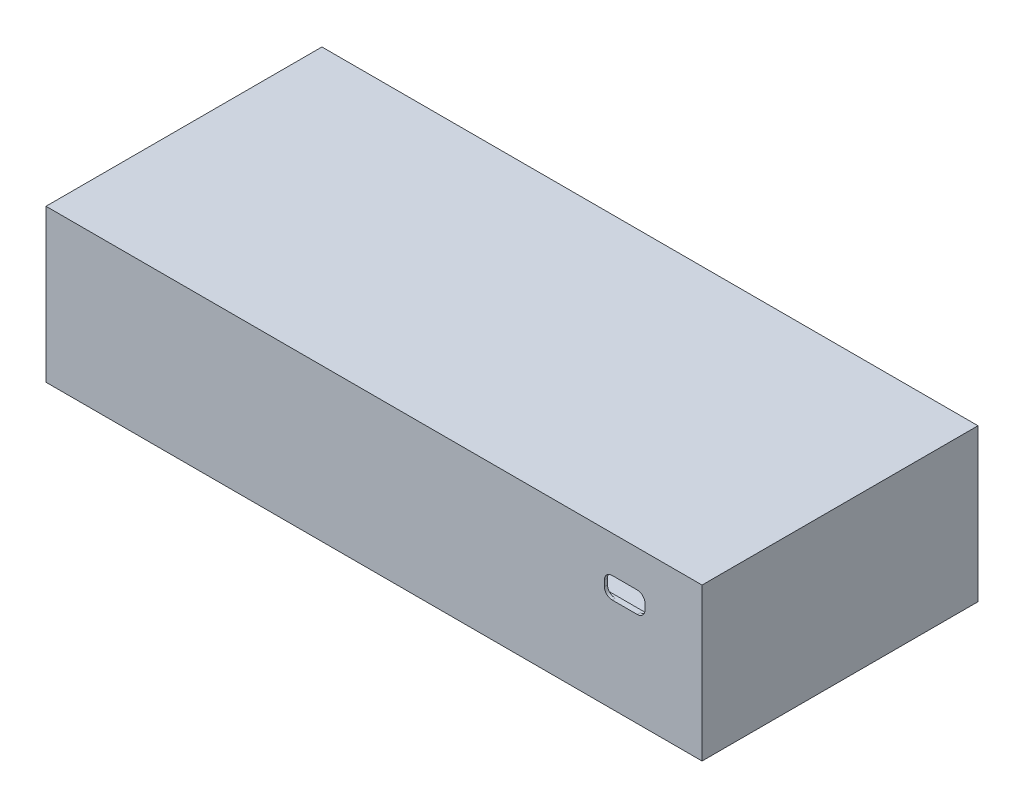
SolidWorks part; units mm, degrees
ref_plane "Front Plane" through (0, 0, 0) normal (0, 0, 1) x (1, 0, 0)
ref_plane "Top Plane" through (0, 0, 0) normal (0, 1, 0) x (1, 0, 0)
ref_plane "Right Plane" through (0, 0, 0) normal (1, 0, 0) x (0, 0, -1)
sketch "Sketch1" plane through (0, 0, 0) normal (0, 1, 0) x (1, 0, 0)
  line L4 (-25, 0) -> (25, 0) construction
  line L6 (-25, -35.75) -> (25, -35.75)
  line L7 (-25, -35.75) -> (-25, 35.75)
  line L8 (-25, 35.75) -> (25, 35.75)
  line L9 (25, -35.75) -> (25, 35.75)
  point P11 (0, 0)
  point P12 (0, 0)
  dimension "D1" = 50
  dimension "D2" = 71.5
extrude "Boss-Extrude1" add sketch "Sketch1" along normal blind 2
sketch "Sketch2" plane through (0, 2, 0) normal (0, 1, 0) x (1, 0, 0)
  line L1 (-11.5, -6.25) -> (11.5, -6.25)
  line L2 (-11.5, -6.25) -> (-11.5, 6.25)
  line L3 (-11.5, 6.25) -> (11.5, 6.25)
  line L4 (11.5, -6.25) -> (11.5, 6.25)
  line L5 (-11.5, -6.25) -> (11.5, 6.25) construction
  line L6 (-11.5, 6.25) -> (11.5, -6.25) construction
  point P0 (0, 0)
  dimension "D1" = 23
  dimension "D2" = 12.5
extrude "Cut-Extrude1" cut sketch "Sketch2" against normal blind 3
sketch "Sketch3" plane through (0, 2, 0) normal (0, 1, 0) x (1, 0, 0)
  line L0 (0, 0) -> (0, 12.615) construction
  line L1 (-13.9, 0) -> (0, 0) construction
  circle A0 centre (-13.9, 0) radius 1.25
  circle A1 centre (-13.9, 0) radius 1.25
  circle A2 centre (13.9, 0) radius 1.25
  circle A3 centre (13.9, 0) radius 1.25
  dimension "D1" = 2.5
  dimension "D2" = 13.9
extrude "Cut-Extrude2" cut sketch "Sketch3" against normal blind 3 contours A0 | A2 region at (-13.9, 2, 0) region at (13.9, 2, 0)
sketch "Sketch4" plane through (0, 2, 0) normal (0, 1, 0) x (1, 0, 0)
  line L0 (-15, -35.75) -> (-25, -35.75)
  line L1 (-25, -35.75) -> (25, -35.75) construction
  line L2 (-25, -35.75) -> (-25, -25.75)
  line L3 (-25, 35.75) -> (-25, -35.75) construction
  line L4 (-15, -35.75) -> (-15, -34.25)
  line L5 (-15, -34.25) -> (-23.5, -34.25)
  line L6 (-23.5, -34.25) -> (-23.5, -25.75)
  line L7 (-23.5, -25.75) -> (-25, -25.75)
  line L8 (25, -35.75) -> (25, 35.75)
  line L9 (25, 35.75) -> (-25, 35.75)
  line L10 (-25, 35.75) -> (-25, -35.75)
  line L11 (-25, -35.75) -> (25, -35.75)
  line L12 (25, -35.75) -> (25, 35.75)
  line L13 (25, 35.75) -> (-25, 35.75)
  line L14 (-25, 35.75) -> (-25, -25.75)
  line L15 (-15, -35.75) -> (25, -35.75)
  line M12 (-25, 35.75) -> (-25, -35.75)
  line M13 (-25, -35.75) -> (25, -35.75)
  dimension "D1" = 10
  dimension "D3" = 1.5
  dimension "D2" = 0
ref_plane "Plane1" [suppressed] through (0, 0, 23.5) normal (0, 0, 1) x (1, 0, 0)
extrude "Boss-Extrude2" [suppressed] add sketch "Sketch4" along normal blind 17 contours L6 L7 L4 L5 M12 M13
sketch "Sketch9" [suppressed] plane through (0, 10, 0) normal (0, 1, 0) x (1, 0, 0)
  line L0 (-25, -25) -> (-25, -15)
  line L1 (-25, -15) -> (-23.5, -15)
  line L2 (-23.5, -15) -> (-23.5, -23.5)
  line L3 (-23.5, -23.5) -> (-15, -23.5)
  line L4 (-15, -23.5) -> (-15, -25)
  line L5 (-15, -25) -> (-25, -25)
ref_plane "Plane2" [suppressed] through (-14.4772, 25.0753, 0) normal (-0.5, 0.866, 0) x (0, 0, 1)
ref_plane "Plane3" [suppressed] through (0, 22, 22) normal (0, 0.7071, 0.7071) x (1, 0, 0)
sketch "Sketch10" [suppressed] plane through (-14.4772, 25.0753, 0) normal (-0.5, 0.866, 0) x (0, 0, 1)
  line L0 (15, -12.1506) -> (15, -10.6506)
  line L1 (15, -10.6506) -> (23.2679, -10.6506)
  line L4 (25, -12.1506) -> (15, -12.1506)
  line L5 (25, -12.1506) -> (23.2679, -10.6506)
  point P10 (23.5, -10.8516)
  dimension "D1" = 1.5
sketch "Sketch12" [suppressed] plane through (0, 19, 0) normal (0, 1, 0) x (1, 0, 0)
  line L0 (-20, -15) -> (-20, -25) construction
  line L1 (-25, -15) -> (-15, -15)
  line L2 (-25, -15) -> (-25, -25)
  line L3 (-25, -25) -> (-15, -25)
  line L4 (-15, -15) -> (-15, -25)
  line L6 (-27.5, -27.5) -> (-12.5, -27.5)
  line L7 (-27.5, -27.5) -> (-27.5, -12.5)
  line L8 (-27.5, -12.5) -> (-12.5, -12.5)
  line L9 (-12.5, -27.5) -> (-12.5, -12.5)
  line L10 (-27.5, -27.5) -> (-12.5, -12.5) construction
  line L11 (-27.5, -12.5) -> (-12.5, -27.5) construction
  point P8 (-20, -20)
  line M3 (-23.5, -23.5) -> (-23.5, -15)
  line M4 (-23.5, -15) -> (-25, -15)
  line M5 (-25, -15) -> (-25, -25)
  line M6 (-25, -25) -> (-15, -25)
  line M7 (-15, -25) -> (-15, -23.5)
  line M8 (-15, -23.5) -> (-23.5, -23.5)
  dimension "D1" = 15
extrude "Boss-Extrude6" [suppressed] add sketch "Sketch12" along normal blind 2 contours L4 L1 M3 M8 | L6 L9 L8 L7 L1 L4 M7 M6 M5 M4 | M8 M3 M4 M5 M6 M7
sketch "Sketch13" [suppressed] plane through (0, 0, 0) normal (0, -1, 0) x (1, 0, 0)
  point P0 (0, 0)
ref_axis "Axis1" [suppressed] through (0, -1.85, 0) along (0, 1, 0)
pattern_circular "CirPattern2" [suppressed] count 4 over 360 about axis through (0, -1.85, 0) along (0, 1, 0) of bodies 107
fillet "Fillet2" [suppressed] radius 5
fillet "Fillet3" [suppressed] radius 6
sketch "Sketch14" plane through (0, 0, 0) normal (0, -1, 0) x (1, 0, 0)
  line L1 (-25, 35.75) -> (-145, 35.75)
  line L2 (-25, 35.75) -> (-25, -35.75)
  line L3 (-25, -35.75) -> (-145, -35.75)
  line L4 (-145, 35.75) -> (-145, -35.75)
  line L5 (25, -35.75) -> (-25, -35.75) construction
  dimension "D1" = 120
extrude "Boss-Extrude7" add sketch "Sketch14" against normal blind 2
sketch "Sketch15" plane through (0, 2, 0) normal (0, 1, 0) x (1, 0, 0)
  line L2 (-145, -35.75) -> (-145, 35.75) construction
  line L3 (25, -35.75) -> (-145, -35.75)
  line L4 (25, -35.75) -> (25, -34.25)
  line L5 (25, -34.25) -> (-145, -34.25)
  line L6 (-145, -35.75) -> (-145, -34.25)
  line L7 (-145, 0) -> (-95.2654, 0) construction
  line L8 (-145, 35.75) -> (-145, 34.25)
  line L9 (25, 34.25) -> (-145, 34.25)
  line L10 (25, 35.75) -> (25, 34.25)
  line L11 (25, 35.75) -> (-145, 35.75)
  dimension "D1" = 1.5
extrude "Boss-Extrude8" add sketch "Sketch15" along normal blind 37.5
sketch "Sketch16" plane through (0, 2, 0) normal (0, 1, 0) x (1, 0, 0)
  line L0 (-145, 34.25) -> (25, 34.25) construction
  line L1 (25, -34.25) -> (23.2, -34.25)
  line L2 (25, -34.25) -> (25, 34.25)
  line L3 (25, 34.25) -> (23.2, 34.25)
  line L4 (23.2, -34.25) -> (23.2, 34.25)
  dimension "D1" = 1.8
extrude "Boss-Extrude9" add sketch "Sketch16" along normal blind 37.5
sketch "Sketch17" plane through (0, 0, 34.25) normal (0, 0, -1) x (-1, 0, 0)
  line L0 (60.9, 39.5) -> (60.9, 30) construction
  line L1 (-23.2, 39.5) -> (145, 39.5) construction
  line L2 (-23.2, 30) -> (145, 30)
  line L3 (145, 39.5) -> (145, 2) construction
  line L4 (60.9, 30) -> (60.9, 24.5) construction
  line L5 (145, 24.5) -> (-23.2, 24.5)
  line L6 (-23.2, 39.5) -> (-23.2, 2) construction
  line L7 (-23.2, 30) -> (-23.2, 24.5)
  line L8 (145, 30) -> (145, 24.5)
  point P9 (60.9, 30)
  point P15 (60.9, 24.5)
  dimension "D1" = 9.5
  dimension "D2" = 5.5
extrude "Cut-Extrude3" cut sketch "Sketch17" against normal blind 0.7
sketch "Sketch18" plane through (0, 0, 34.95) normal (0, 0, -1) x (-1, 0, 0)
  line L0 (-23.2, 27.25) -> (-10.2, 27.25) construction
  line L1 (-23.2, 30) -> (-23.2, 24.5) construction
  line L2 (-10.2, 27.25) -> (0.3, 27.25) construction
  line L3 (145, 30) -> (-23.2, 30) construction
  line L4 (0.3, 27.25) -> (-10.2, 27.25)
  line L5 (0.3, 24.5) -> (0.3, 30)
  line L6 (0.3, 30) -> (-10.2, 30)
  line L7 (-10.2, 24.5) -> (-10.2, 30)
  line L8 (0.3, 24.5) -> (-10.2, 24.5)
  line M5 (145, 30) -> (-23.2, 30)
  line M7 (-23.2, 24.5) -> (145, 24.5)
  dimension "D1" = 13
  dimension "D2" = 10.5
extrude "Cut-Extrude4" cut sketch "Sketch18" against normal blind 1 contours L7 L4 L5 M5 | L7 L5 L4 M7 region at (4.95, 25.875, 34.95) region at (4.95, 28.625, 34.95)
fillet "Fillet4" radius 2 4 edges at (10.2, 24.5, 35.35) (10.2, 30, 35.35) (-0.3, 30, 35.35) (-0.3, 24.5, 35.35)
sketch "Sketch19" plane through (23.2, 0, 0) normal (-1, 0, 0) x (0, 0, 1)
  line L0 (34.25, 39.5) -> (34.25, 30) construction
  line L1 (-34.25, 39.5) -> (34.25, 39.5)
  line L2 (-34.25, 39.5) -> (-34.25, 37)
  line L3 (-34.25, 37) -> (34.25, 37)
  line L4 (34.25, 39.5) -> (34.25, 37)
  dimension "D1" = 2.5
extrude "Boss-Extrude10" add sketch "Sketch19" along normal up to surface (168.2 mm away) up to face at (-145, 22.5833, 11.5333)
chamfer "Chamfer1" distance 0.5 angle 45 1 edges at (-60.9, 30, 34.25)
